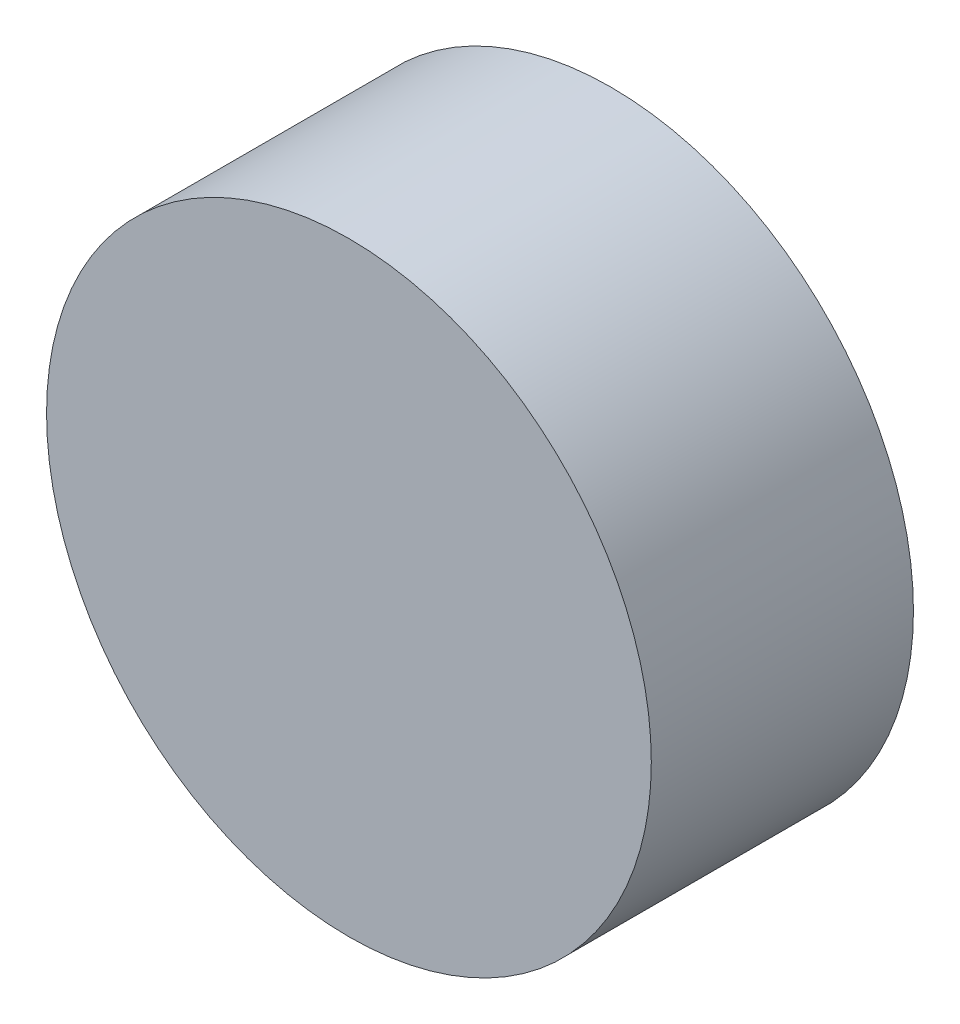
SolidWorks part; units mm, degrees
material "Filter_Bulk_6061Properties"
ref_plane "Front Plane" through (0, 0, 0) normal (0, 0, 1) x (1, 0, 0)
ref_plane "Top Plane" through (0, 0, 0) normal (0, 1, 0) x (1, 0, 0)
ref_plane "Right Plane" through (0, 0, 0) normal (1, 0, 0) x (0, 0, -1)
sketch "Sketch1" plane through (0, 0, 0) normal (0, 0, 1) x (1, 0, 0)
  circle A0 centre (0, 0) radius 13.15
  point P2 (0, 0)
  dimension "D1" = 26.3
extrude "Boss-Extrude1" add sketch "Sketch1" along normal blind 11.4
